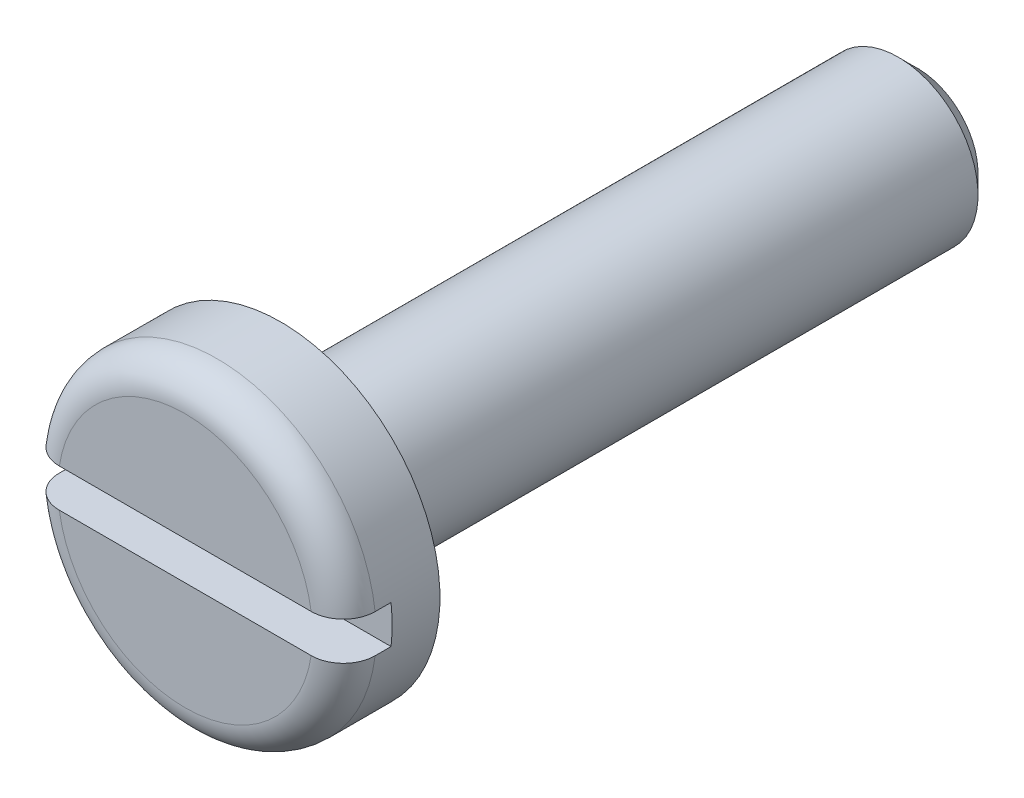
SolidWorks part; units mm, degrees
material "Простая углеродистая сталь"
ref_plane "Спереди" through (0, 0, 0) normal (0, 0, 1) x (1, 0, 0)
ref_plane "Сверху" through (0, 0, 0) normal (0, 1, 0) x (1, 0, 0)
ref_plane "Справа" through (0, 0, 0) normal (1, 0, 0) x (0, 0, -1)
sketch "Эскиз1" plane through (0, 0, 0) normal (0, 1, 0) x (1, 0, 0)
  line L0 (0, 0) -> (-5, 0)
  line L1 (-5, 0) -> (-5, 3)
  line L2 (-5, 3) -> (-2.5, 3)
  line L3 (-2.5, 3) -> (-2.5, 23)
  line L4 (-2.5, 23) -> (0, 23)
  line L5 (0, 23) -> (0, 0)
  dimension "D1" = 5
  dimension "D2" = 3
  dimension "D3" = 23
  dimension "D4" = 2.5
revolve "Повернуть1" add sketch "Эскиз1" angle 360 about L5
sketch "Эскиз2" plane through (0, 0, 0) normal (1, 0, 0) x (0, 0, -1)
  line L0 (0, 0) -> (22.6818, 0) construction
  line L1 (0, -0.6) -> (0, 0.6)
  line L2 (0, 0.6) -> (1.5, 0.6)
  line L3 (0, -0.6) -> (1.5, -0.6)
  line L4 (1.5, 0.6) -> (1.5, -0.6)
  point P7 (0, 0)
  point P10 (1.5, 0)
  dimension "D1" = 1.2
  dimension "D2" = 1.5
extrude "Вырез-Вытянуть1" cut sketch "Эскиз2" against normal through all both and the other way through all
chamfer "Фаска1" distance 0.6 angle 45 1 edges at (-2.5, 0, -23)
fillet "Скругление1" radius 1 2 edges at (0, -5, 0) (0, 5, 0)
fillet "Скругление2" radius 0.4 1 edges at (-2.5, 0, -3)
